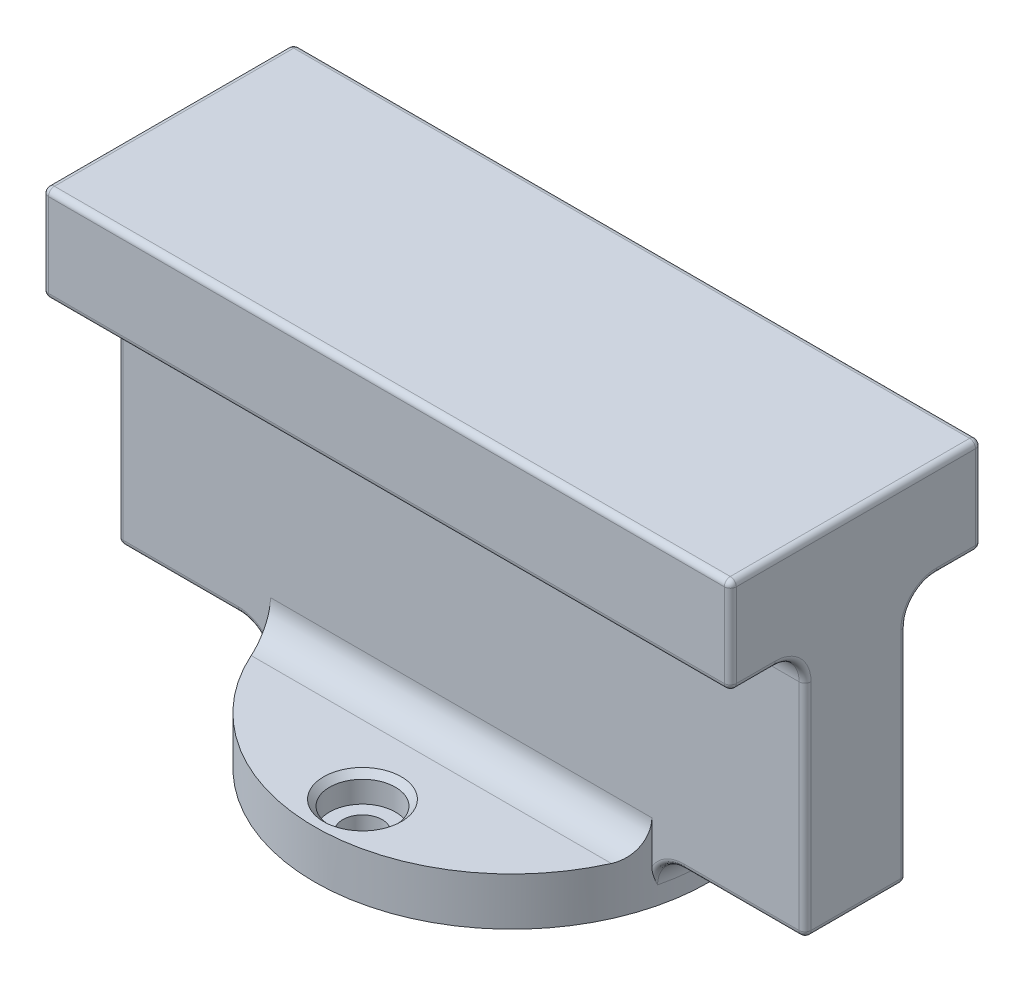
SolidWorks part; units mm, degrees
ref_plane "Front Plane" through (0, 0, 0) normal (0, 0, 1) x (1, 0, 0)
ref_plane "Top Plane" through (0, 0, 0) normal (0, 1, 0) x (1, 0, 0)
ref_plane "Right Plane" through (0, 0, 0) normal (1, 0, 0) x (0, 0, -1)
sketch "Sketch1" plane through (0, 0, 0) normal (0, 1, 0) x (1, 0, 0)
  circle A5 centre (0, 0) radius 33
  dimension "D1" = 66
extrude "Boss-Extrude1" add sketch "Sketch1" along normal blind 8
sketch "Sketch2" plane through (0, 0, 0) normal (0, -1, 0) x (-1, 0, 0)
  circle A0 centre (0, 0) radius 15.5
  dimension "D1" = 31
extrude "Boss-Extrude2" add sketch "Sketch2" along normal blind 3
sketch "Sketch4" plane through (0, 0, 0) normal (0, -1, 0) x (1, 0, 0)
  circle A0 centre (-17.6777, -17.6777) radius 3.15
  dimension "D2" = 6.3
extrude "Cut-Extrude2" cut sketch "Sketch4" against normal blind 5
chamfer "Chamfer1" distance 0.5 angle 45 1 edges at (0, -3, -15.5)
sketch "Sketch5" plane through (0, 0, 0) normal (0, -1, 0) x (1, 0, 0)
  line L0 (0, 33) -> (0, -33) construction
  line L1 (-33, 0) -> (33, 0) construction
  circle A0 centre (0, 0) radius 33 construction
hole_wizard "CBORE for M6 Hex Socket Thin Head Cap Screw3" positions "Sketch9" profile "Sketch10" counterbore size "M6" standard "DIN" end condition through all
sketch "Sketch9" plane through (0, 8, 0) normal (0, 1, 0) x (1, 0, 0)
  line L0 (0, -33) -> (0, 33) construction
  point P0 (0, 25)
  point P4 (0, -25)
  dimension "D1" = 25
  dimension "D2" = 25
sketch "Sketch10" plane through (0, 8, -25) normal (1, 0, 0) x (0, 0, 1)
  line L0 (0, 0) -> (0, 11)
  line L1 (0, 11) -> (3.3, 11)
  line L3 (3.3, 11) -> (3.3, 4.6)
  line L4 (5.5, 4.6) -> (3.3, 4.6)
  line L5 (5.5, 4.6) -> (5.5, 1)
  line L6 (5.5, 1) -> (6.5, 0)
  line L7 (6.5, 0) -> (0, 0)
  line L8 (-5.5, 1) -> (-6.5, 0) construction
  line L11 (0, -6.35) -> (0, 107.95) construction
  dimension "Thru Hole Dia." = 6.6
  dimension "Thru Hole Depth" = 11
  dimension "C'Bore Dia." = 11
  dimension "C'Bore Depth" = 4.6
  dimension "Near C'Sink Dia." = 13
  dimension "Near C'Sink Angle" = 90
hole_wizard "CSK for M4 Countersunk Flat Head Screw1" positions "Sketch11" profile "Sketch12" countersink size "M4" standard "DIN" end condition through all
sketch "Sketch11" plane through (0, -3, 0) normal (0, -1, 0) x (-1, 0, 0)
  point P0 (0, 0)
sketch "Sketch12" plane through (0, -3, 0) normal (1, 0, 0) x (0, 0, -1)
  line L0 (0, 0) -> (0, 11)
  line L1 (0, 11) -> (2.25, 11)
  line L2 (2.25, 11) -> (2.25, 2.45)
  line L3 (2.25, 2.45) -> (4.7, 0)
  line L5 (4.7, 0) -> (0, 0)
  line L6 (-2.25, 2.45) -> (-4.7, 0) construction
  line L11 (0, -6.35) -> (0, 107.95) construction
  dimension "Thru Hole Dia." = 4.5
  dimension "Thru Hole Depth" = 11
  dimension "Near C'Sink Dia." = 9.4
  dimension "Near C'Sink Angle" = 90
sketch "Sketch13" plane through (0, 8, 0) normal (0, 1, 0) x (1, 0, 0)
  line L0 (0, -8.5) -> (0, 8.5) construction
  line L1 (-57.5, -8.5) -> (57.5, -8.5)
  line L2 (57.5, -8.5) -> (57.5, 8.5)
  line L3 (57.5, 8.5) -> (-57.5, 8.5)
  line L4 (-57.5, 8.5) -> (-57.5, -8.5)
  point P5 (0, 0)
  point P9 (0, -8.5)
  dimension "D1" = 17
  dimension "D2" = 115
extrude "Boss-Extrude3" add sketch "Sketch13" along normal blind 42
sketch "Sketch14" plane through (0, 50, 0) normal (0, 1, 0) x (1, 0, 0)
  line L0 (0, -21) -> (0, 21) construction
  line L1 (-57.5, -21) -> (-57.5, 21)
  line L2 (-57.5, -21) -> (57.5, -21)
  line L3 (-57.5, 21) -> (57.5, 21)
  line L4 (57.5, -21) -> (57.5, 21)
  line L5 (-57.5, -21) -> (57.5, 21) construction
  line L6 (-57.5, 21) -> (57.5, -21) construction
  point P5 (0, 0)
  point P7 (0, 0)
  dimension "D1" = 42
  dimension "D2" = 115
extrude "Boss-Extrude4" add sketch "Sketch14" along normal blind 16
fillet "Fillet1" radius 5 4 edges at (0, 8, 8.5) (0, 8, -8.5) (0, 50, 8.5) (0, 50, -8.5)
fillet "Fillet2" radius 5 2 edges at (-33, 8, 0) (33, 8, 0)
fillet "Fillet3" radius 1 32 edges at (-33.7534, 6.8479, 8.5) (-32.9576, 6.0474, -8.5) (33.7534, 6.8479, -8.5) (32.9576, 6.0474, 8.5) (-47.2686, 8, 8.5) (-47.2686, 8, -8.5) (47.2686, 8, -8.5) (47.2686, 8, 8.5) (0, 66, 21) (0, 50, 21) (57.5, 26.5, 8.5) (57.5, 48.5355, 9.9645) (57.5, 50, 17.25) (57.5, 58, 21) (57.5, 66, 0) (57.5, 50, -17.25) (57.5, 48.5355, -9.9645) (57.5, 26.5, -8.5) (57.5, 8, 0) (57.5, 58, -21) (0, 66, -21) (0, 50, -21) (-57.5, 26.5, -8.5) (-57.5, 48.5355, -9.9645) (-57.5, 50, -17.25) (-57.5, 58, -21) (-57.5, 66, 0) (-57.5, 58, 21) (-57.5, 50, 17.25) (-57.5, 48.5355, 9.9645) (-57.5, 26.5, 8.5) (-57.5, 8, 0)
